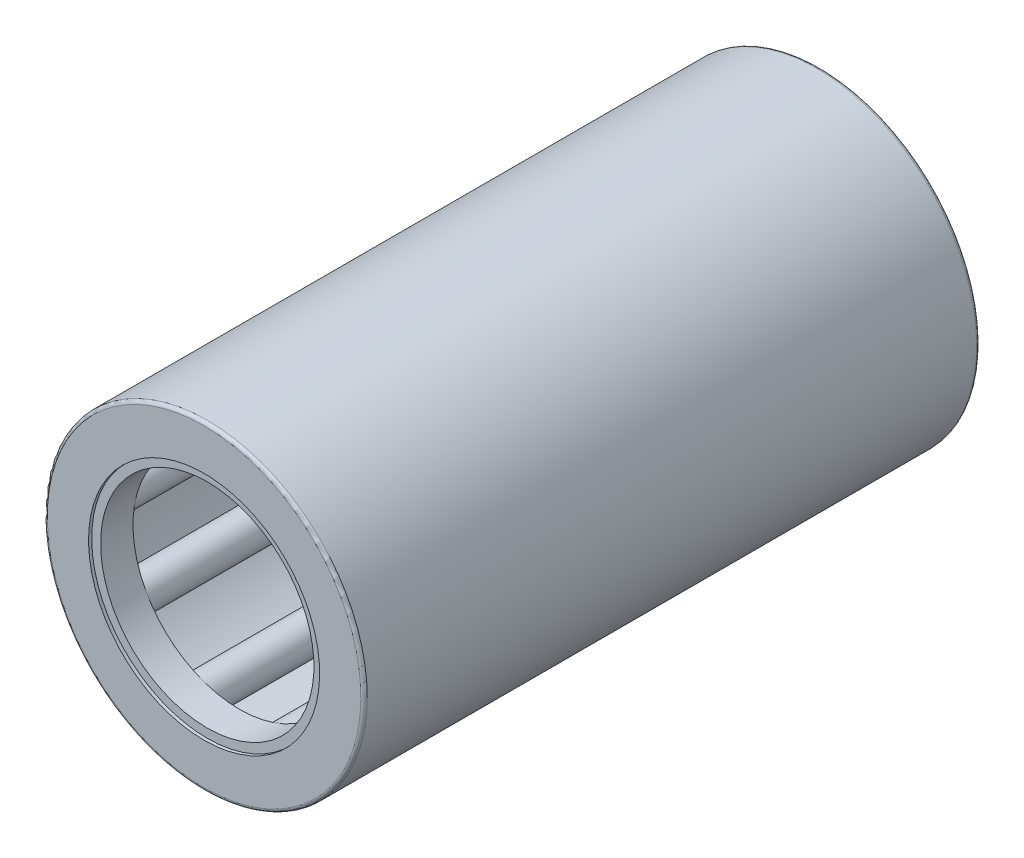
SolidWorks part; units mm, degrees
ref_plane "Front Plane" through (0, 0, 0) normal (0, 0, 1) x (1, 0, 0)
ref_plane "Top Plane" through (0, 0, 0) normal (0, 1, 0) x (1, 0, 0)
ref_plane "Right Plane" through (0, 0, 0) normal (1, 0, 0) x (0, 0, -1)
sketch "Sketch1" plane through (0, 0, 0) normal (1, 0, 0) x (0, 0, -1)
  line L0 (-13.75, 0) -> (13.75, 0) construction
  line L1 (0, 0) -> (0, 7.1438) construction
  line L2 (-13.75, 0) -> (-13.75, 7.1437) construction
  line L3 (-13.75, 7.1437) -> (13.75, 7.1437)
  line L4 (13.75, 7.1437) -> (13.75, 0) construction
  line L5 (13.75, 0) -> (12.9563, 0) construction
  line L6 (12.9563, 0) -> (12.9563, 6.35) construction
  line L7 (12.9563, 6.35) -> (-12.9563, 6.35)
  line L8 (-12.9563, 6.35) -> (-12.9563, 0) construction
  line L9 (-12.9563, 0) -> (-13.75, 0) construction
  line L10 (-13.75, 7.1437) -> (-13.75, 5.1594)
  line L11 (-13.75, 5.1594) -> (-12.9563, 5.1594)
  line L12 (-12.9563, 5.1594) -> (-12.9563, 6.35)
  line L13 (12.9563, 7.1437) -> (12.9563, 6.35) construction
  line L14 (12.9563, 6.35) -> (12.9563, 5.1594)
  line L15 (12.9563, 5.1594) -> (13.75, 5.1594)
  line L16 (13.75, 5.1594) -> (13.75, 7.1437)
  line L17 (12.9563, 6.35) -> (12.9563, 5.5562) construction
  line L18 (12.9563, 5.5562) -> (12.9563, 4.7625) construction
  point P5 (0, 4.7625)
  dimension "Width" = 27.5
  dimension "OD" = 14.2875
  dimension "Shaft Dia" = 9.525
revolve "Revolve1" add sketch "Sketch1" angle 360 about L0
sketch "Sketch2" plane through (0, 0, 0) normal (1, 0, 0) x (0, 0, -1)
  line L0 (12.9563, 6.35) -> (-12.9563, 6.35) construction
  line L1 (-12.1625, 5.5562) -> (12.1625, 5.5562) construction
  line L2 (-12.1625, 5.5562) -> (-12.1625, 6.35) construction
  line L3 (-12.1625, 6.35) -> (12.1625, 6.35)
  line L4 (12.1625, 5.5562) -> (12.1625, 6.35) construction
  line L5 (12.9563, 5.1594) -> (13.75, 5.1594) construction
  line L6 (-12.9563, 5.5562) -> (-12.1625, 5.5562) construction
  line L7 (12.1625, 5.5562) -> (12.9563, 5.5562) construction
  line L8 (-13.75, 5.1594) -> (-12.9563, 5.1594) construction
  line L9 (-12.1625, 5.7547) -> (-12.1625, 5.3578) construction
  line L10 (-12.9563, 5.5562) -> (-12.9563, 5.1594) construction
  line L11 (-12.1625, 6.35) -> (-12.1625, 5.7547)
  line L12 (12.1625, 6.35) -> (12.1625, 5.7547)
  line L13 (12.1625, 5.7547) -> (-12.1625, 5.7547)
  line L14 (0, 6.35) -> (0, 4.7625) construction
  line L15 (-12.9563, 5.1594) -> (-12.9563, 6.35) construction
  line L16 (-12.1625, 5.3578) -> (-12.9563, 5.3578) construction
  line L17 (0, 0) -> (13.75, 0) construction
  line L31 (13.75, -7.1438) -> (13.75, 7.1437) construction
  point P16 (0, 5.5563)
revolve "Revolve2" add sketch "Sketch2" angle 360 about L1
sketch "Sketch3" plane through (0, 0, 0) normal (1, 0, 0) x (0, 0, -1)
  line L0 (12.9563, 6.35) -> (12.9563, 5.1594) construction
  line L1 (-12.9563, 5.5562) -> (12.9563, 5.5562)
  line L2 (-12.9563, 5.5562) -> (-12.9563, 5.7547)
  line L3 (-12.9563, 5.7547) -> (12.9563, 5.7547)
  line L4 (12.9563, 5.5562) -> (12.9563, 5.7547)
  line L5 (0, 0) -> (13.75, 0) construction
  line L6 (13.75, -7.1438) -> (13.75, 7.1437) construction
revolve "Revolve3" add sketch "Sketch3" angle 360 about L1
ref_axis "Axis1" through (0, 0, -13.75) along (0, 0, 1)
pattern_circular "CirPattern1" count 9 every 40 about axis through (0, 0, -13.75) along (0, 0, 1) of bodies 166 167
fillet "Fillet1" radius 0.1429 2 edges at (0, -7.1438, -13.75) (0, -7.1438, 13.75)
sketch "Sketch4" plane through (0, 0, 0) normal (1, 0, 0) x (0, 0, -1)
  line L1 (13.6071, 4.7625) -> (12.1625, 4.7625)
  line L2 (13.6071, 4.7625) -> (13.6071, 5.1594)
  line L3 (13.6071, 5.1594) -> (12.1625, 5.1594)
  line L4 (12.1625, 4.7625) -> (12.1625, 5.1594)
  line L5 (-13.75, 5.1594) -> (-12.9563, 5.1594) construction
  line L6 (13.6071, -7.1438) -> (13.6071, 7.1437) construction
  line L7 (12.1625, 6.35) -> (12.1625, 5.7547) construction
revolve "Revolve4" add sketch "Sketch4" angle 360 about L0
sketch "Sketch5" plane through (0, 0, 0) normal (1, 0, 0) x (0, 0, -1)
  line L0 (-13.6071, 7.1437) -> (-13.6071, -7.1438) construction
  line L1 (-12.1625, 4.7625) -> (-13.6071, 4.7625)
  line L2 (-12.1625, 4.7625) -> (-12.1625, 5.1594)
  line L3 (-12.1625, 5.1594) -> (-13.6071, 5.1594)
  line L4 (-13.6071, 4.7625) -> (-13.6071, 5.1594)
  line L6 (-12.1625, 6.35) -> (-12.1625, 5.7547) construction
  line L7 (-13.75, 5.1594) -> (-12.9563, 5.1594) construction
revolve "Revolve5" add sketch "Sketch5" angle 360 about L0
sketch "Front View" plane through (0, 0, 0) normal (0, 0, 1) x (1, 0, 0)
  circle A0 centre (0, 0) radius 4.7625 construction
  circle A1 centre (0, 0) radius 7.1438 construction
  dimension "OD" = 14.2875
  dimension "ID" = 9.525
sketch "Right View" plane through (0, 0, 0) normal (1, 0, 0) x (0, 0, -1)
  line L0 (-13.75, 7.1438) -> (13.75, 7.1438) construction
  dimension "Width" = 27.5
ref_axis "Center Axis 1" through (0, 0, -13.6071) along (0, 0, 1)
ref_plane "Contact Plane 1" through (0, 0, 13.75) normal (0, 0, 1) x (1, 0, 0)
ref_plane "Contact Plane 2" through (0, 0, -13.75) normal (0, 0, -1) x (-1, 0, 0)
equation "\"Rollers@CirPattern1\" = \"OD@Sketch1\"*16"
equation "\"D1@Fillet1\" = \"OD@Sketch1\"*.01"
equation "\"Angle@CirPattern1\"= 360 / \"Rollers@CirPattern1\""
equation "\"OD@Front View\"=\"OD@Sketch1\""
equation "\"ID@Front View\"=\"Shaft Dia@Sketch1\""
equation "\"Width@Right View\"=\"Width@Sketch1\""
